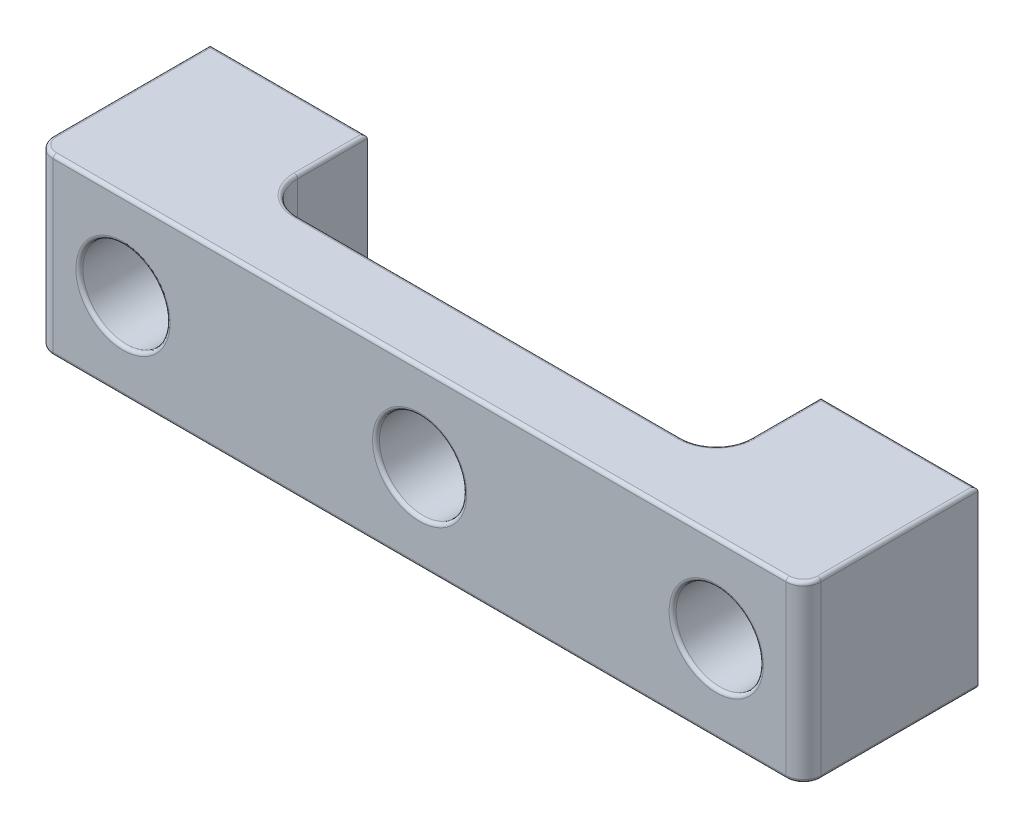
SolidWorks part; units mm, degrees
ref_plane "Ön Düzlem" through (0, 0, 0) normal (0, 0, 1) x (1, 0, 0)
ref_plane "Üst Düzlem" through (0, 0, 0) normal (0, 1, 0) x (1, 0, 0)
ref_plane "Sağ Düzlem" through (0, 0, 0) normal (1, 0, 0) x (0, 0, -1)
sketch "Sketch1" plane through (0, 0, 0) normal (0, 0, 1) x (1, 0, 0)
  line L0 (-11, 0) -> (11, 0)
  line L1 (11, 0) -> (11, 5)
  line L2 (11, 5) -> (-11, 5)
  line L3 (-11, 0) -> (-11, 5)
  line L4 (0, 5) -> (0, 0) construction
  circle A0 centre (8.5, 2.5) radius 1.25
  circle A1 centre (0, 2.5) radius 1.25
  circle A2 centre (-8.5, 2.5) radius 1.25
  dimension "D2" = 2.5
  dimension "D1" = 22
  dimension "D3" = 2.5
  dimension "D4" = 8.5
  dimension "D5" = 5
extrude "Boss-Extrude1" add sketch "Sketch1" along normal blind 5
sketch "Sketch2" plane through (0, 5, 0) normal (0, 1, 0) x (1, 0, 0)
  line L0 (11, 0) -> (-11, 0) construction
  line L1 (6.5, 0) -> (-6.5, 0)
  line L2 (6.5, 0) -> (6.5, -3)
  line L3 (6.5, -3) -> (-6.5, -3)
  line L4 (-6.5, 0) -> (-6.5, -3)
  line L5 (6.5, 0) -> (-6.5, -3) construction
  line L6 (6.5, -3) -> (-6.5, 0) construction
  point P0 (0, -1.5)
  dimension "D1" = 13
  dimension "D2" = 3
extrude "Cut-Extrude1" cut sketch "Sketch2" against normal through all
fillet "Fillet1" radius 1 2 edges at (6.5, 2.5, 3) (-6.5, 2.5, 3)
fillet "Fillet2" radius 0.5 2 edges at (-11, 2.5, 5) (11, 2.5, 5)
fillet "Fillet3" radius 0.1 27 edges at (10.8536, 0, 4.8536) (11, 0, 2.25) (8.75, 0, 0) (6.5, 0, 1) (6.2071, 0, 2.7071) (0, 0, 3) (-6.2071, 0, 2.7071) (-6.5, 0, 1) (-8.75, 0, 0) (-11, 0, 2.25) (-10.8536, 0, 4.8536) (1.25, 2.5, 5) (-9.75, 2.5, 5) (0, 0, 5) (9.75, 2.5, 5) (-8.75, 5, 0) (-6.5, 5, 1) (-6.2071, 5, 2.7071) (0, 5, 3) (6.2071, 5, 2.7071) (6.5, 5, 1) (8.75, 5, 0) (11, 5, 2.25) (10.8536, 5, 4.8536) (0, 5, 5) (-10.8536, 5, 4.8536) (-11, 5, 2.25)
ref_plane "Plane1" through (0, 0, 3) normal (0, 0, -1) x (-1, 0, 0)
ref_axis "Axis1" through (0, -0.25, 3) along (0, 1, 0)
